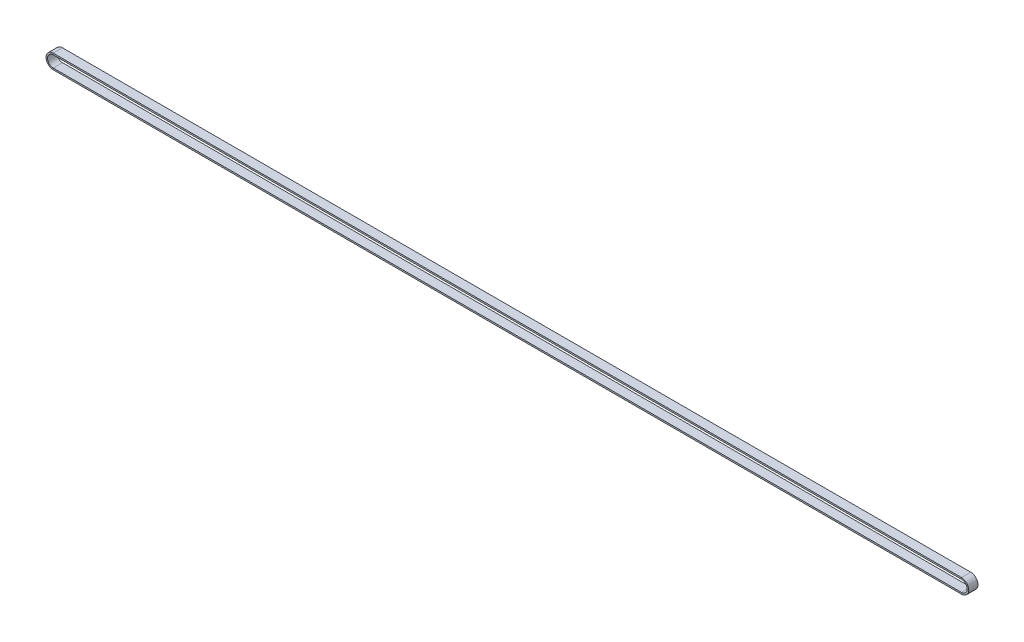
SolidWorks part; units mm, degrees
ref_plane "Front Plane" through (0, 0, 0) normal (0, 0, 1) x (1, 0, 0)
ref_plane "Top Plane" through (0, 0, 0) normal (0, 1, 0) x (1, 0, 0)
ref_plane "Right Plane" through (0, 0, 0) normal (1, 0, 0) x (0, 0, -1)
sketch "Sketch2" plane through (0, 0, 0) normal (0, 0, 1) x (1, 0, 0)
  line L0 (0, 0) -> (1, 0) construction
  line L1 (0, 0) -> (0, 1) construction
  line L2 (0, 2.1382) -> (882.5203, 2.1382)
  line L3 (882.5203, -11.8618) -> (0, -11.8618)
  arc A0 (0, -11.8618) -> (0, 2.1382) centre (0, -4.8618) cw
  arc A1 (882.5203, 2.1382) -> (882.5203, -11.8618) centre (882.5203, -4.8618) cw
sketch "Sketch3" plane through (0, 0, 0) normal (1, 0, 0) x (0, 0, -1)
  line L1 (0, 0.6382) -> (-9, 0.6382)
  line L2 (0, 0.6382) -> (0, 2.1382)
  line L3 (0, 2.1382) -> (-9, 2.1382)
  line L4 (-9, 0.6382) -> (-9, 2.1382)
  dimension "D1" = 9
  dimension "D2" = 1.5
sweep "Sweep1" add profiles "Sketch3" path "Sketch2"
